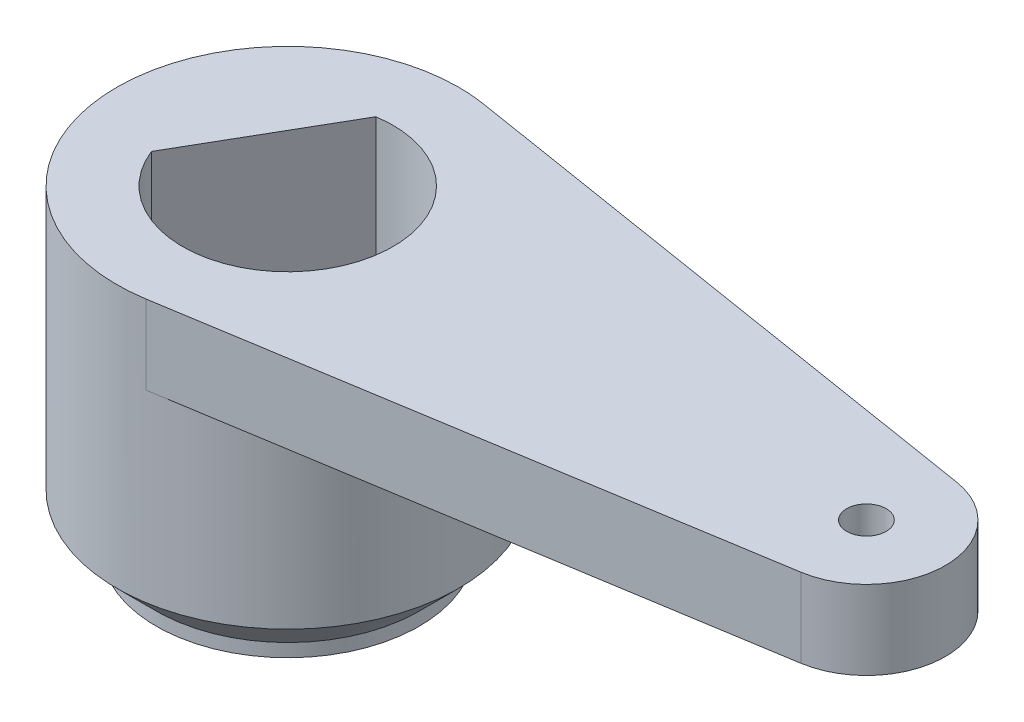
SolidWorks part; units mm, degrees
ref_plane "Front Plane" through (0, 0, 0) normal (0, 0, 1) x (1, 0, 0)
ref_plane "Top Plane" through (0, 0, 0) normal (0, 1, 0) x (1, 0, 0)
ref_plane "Right Plane" through (0, 0, 0) normal (1, 0, 0) x (0, 0, -1)
sketch "Sketch1" plane through (0, 0, 0) normal (0, 1, 0) x (1, 0, 0)
  circle A0 centre (0, 0) radius 4
  circle A2 centre (0, 0) radius 6.5
  dimension "D1" = 8
  dimension "D2" = 2.5
extrude "Boss-Extrude1" add sketch "Sketch1" along normal blind 12
sketch "Sketch2" plane through (0, 12, 0) normal (0, 1, 0) x (1, 0, 0)
  line L0 (1.0341, 6.4172) -> (22.4773, 2.9618)
  line L1 (1.0341, -6.4172) -> (22.4773, -2.9618)
  line L2 (0, 0) -> (22, 0) construction
  arc A0 (22.4773, -2.9618) -> (22.4773, 2.9618) centre (22, 0) ccw
  circle A1 centre (0, 0) radius 6.5 construction
  circle A2 centre (0, 0) radius 6.5
  circle A3 centre (22, 0) radius 0.75
  circle M6 centre (0, 0) radius 6.5
  dimension "D2" = 6
  dimension "D3" = 1.5
  dimension "D1" = 22
extrude "Boss-Extrude2" add sketch "Sketch2" against normal blind 3 contours L1 A0 L0 A2 M6 region at (13.6374, 12, 0)
sketch "Sketch3" plane through (0, 0, 0) normal (0, -1, 0) x (1, 0, 0)
sketch "Sketch4" plane through (0, 0, 0) normal (0, -1, 0) x (1, 0, 0)
  circle A0 centre (0, 0) radius 4 construction
  circle A1 centre (0, 0) radius 4
  circle A2 centre (0, 0) radius 5
  circle A3 centre (0, 0) radius 6.5 construction
  circle A4 centre (0, 0) radius 6.5
  circle M4 centre (0, 0) radius 6.5
  dimension "D1" = 1
extrude "Cut-Extrude1" cut sketch "Sketch4" against normal blind 2 contours A2 M4 region at (-6.3162, 0, 0)
sketch "Sketch5" plane through (0, 12, 0) normal (0, 1, 0) x (1, 0, 0)
  line L0 (-0.6038, 3.9542) -> (-3.7263, -1.4542)
  line L1 (-2.1651, 1.25) -> (0, 0) construction
  line L2 (0, 0) -> (-4, 0) construction
  circle A0 centre (0, 0) radius 4 construction
  circle A1 centre (0, 0) radius 4
  circle M6 centre (0, 0) radius 4
  dimension "D1" = 2.5
  dimension "D2" = 30
extrude "Boss-Extrude4" add sketch "Sketch5" against normal blind 10 contours L0 M6 region at (-2.6941, 12, -1.5554)
chamfer "Chamfer1" distance 1.5 angle 45 1 edges at (0, 2, -5)
